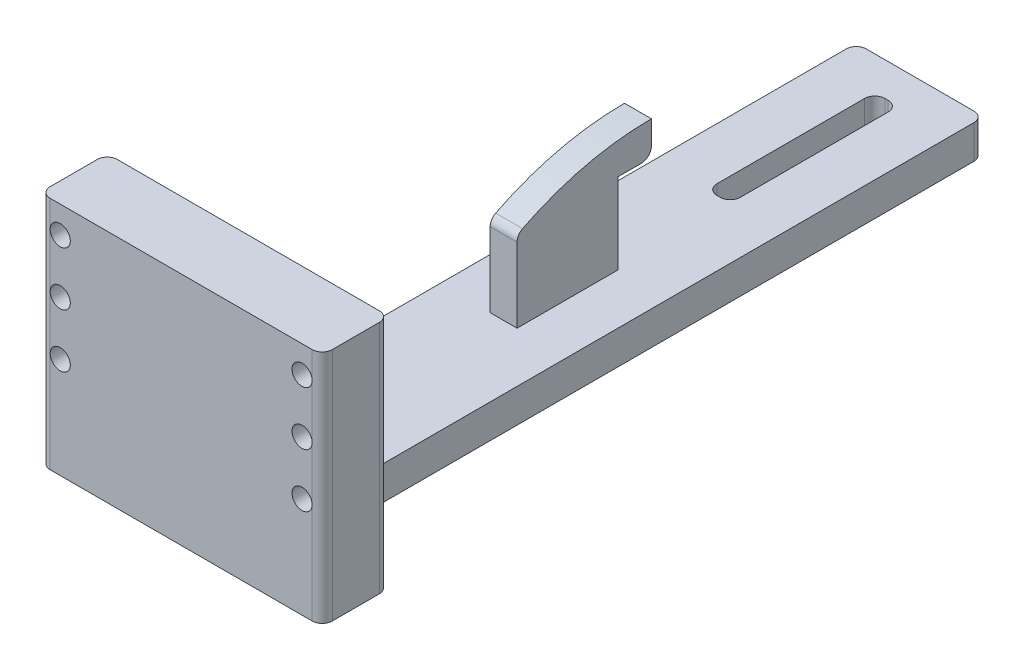
SolidWorks part; units mm, degrees
ref_plane "Front Plane" through (0, 0, 0) normal (0, 0, 1) x (1, 0, 0)
ref_plane "Top Plane" through (0, 0, 0) normal (0, 1, 0) x (1, 0, 0)
ref_plane "Right Plane" through (0, 0, 0) normal (1, 0, 0) x (0, 0, -1)
sketch "Sketch1" plane through (0, 0, 0) normal (0, 1, 0) x (1, 0, 0)
  line L1 (0, 0) -> (-19, 0)
  line L2 (0, 0) -> (0, 110)
  line L3 (0, 110) -> (-19, 110)
  line L4 (-19, 0) -> (-19, 110)
  line L5 (-11.25, 105) -> (-7.75, 105)
  line L6 (-11.25, 105) -> (-11.25, 80)
  line L7 (-11.25, 80) -> (-7.75, 80)
  line L8 (-7.75, 105) -> (-7.75, 80)
  point P9 (-9.5, 105)
  point P10 (-9.5, 110)
  dimension "D1" = 110
  dimension "D2" = 19
  dimension "D3" = 3.5
  dimension "D4" = 5
  dimension "D5" = 25
extrude "Boss-Extrude1" add sketch "Sketch1" along normal blind 5
sketch "Sketch2" plane through (0, 0, 0) normal (1, 0, 0) x (0, 0, -1)
  line L0 (10, 15) -> (10, 35)
  line L2 (0, 5) -> (0, 15)
  line L4 (10, 5) -> (10, 15)
  line L5 (10, 35) -> (0, 35)
  line L6 (0, 35) -> (0, 15)
  line L8 (0, 0) -> (10, 0)
  line L9 (0, 0) -> (0, 5)
  line L11 (10, 0) -> (10, 5)
  line L13 (0, 5) -> (110, 5) construction
  dimension "D1" = 10
  dimension "D2" = 180
  dimension "D3" = 10
  dimension "D4" = 20
  dimension "D5" = 10
extrude "Boss-Extrude2" add sketch "Sketch2" against normal blind 30.5 and the other way blind 11.5
sketch "Sketch3" plane through (0, 0, -10) normal (0, 0, -1) x (-1, 0, 0)
  line L0 (-11.5, 35) -> (30.5, 35) construction
  line L2 (9.5, 35) -> (9.5, 5) construction
  line L3 (19, 5) -> (0, 5) construction
  circle A0 centre (-8.5, 31) radius 1.5
  circle A1 centre (-8.5, 23) radius 1.5
  circle A2 centre (-8.5, 15) radius 1.5
  circle A3 centre (27.5, 15) radius 1.5
  circle A4 centre (27.5, 23) radius 1.5
  circle A5 centre (27.5, 31) radius 1.5
  point P14 (0, 0)
  dimension "D2" = 3
  dimension "D1" = 8
  dimension "D3" = 8
  dimension "D4" = 4
  dimension "D5" = 18
extrude "Cut-Extrude1" cut sketch "Sketch3" against normal blind 10
sketch "Sketch4" plane through (0, 5, 0) normal (0, 1, 0) x (1, 0, 0)
  line L1 (-11.5, 63) -> (-7.5, 63)
  line L2 (-11.5, 63) -> (-11.5, 48)
  line L3 (-11.5, 48) -> (-7.5, 48)
  line L4 (-7.5, 63) -> (-7.5, 48)
  line L5 (0, 110) -> (-19, 110) construction
  line L6 (-19, 10) -> (0, 10) construction
  point P6 (-9.5, 110)
  point P7 (-9.5, 63)
  dimension "D1" = 4
  dimension "D2" = 15
  dimension "D3" = 53
extrude "Boss-Extrude3" add sketch "Sketch4" along normal blind 12
sketch "Sketch5" plane through (-7.5, 0, 0) normal (1, 0, 0) x (0, 0, -1)
  line L0 (63, 17) -> (68, 17)
  line L1 (68, 17) -> (68, 22)
  line L2 (68, 22) -> (78.519, 22) construction
  line L3 (48, 17) -> (63, 17)
  arc A0 (48, 17) -> (68, 22) centre (68, -20.5) cw
  dimension "D1" = 5
  dimension "D2" = 5
extrude "Boss-Extrude4" add sketch "Sketch5" against normal blind 4
fillet "Fillet1" radius 1.5 15 edges at (0, 2.5, -110) (-19, 2.5, -110) (11.5, 17.5, 0) (-30.5, 17.5, 0) (11.5, 17.5, -10) (0, 2.5, -10) (-19, 2.5, -10) (-30.5, 17.5, -10) (-11.25, 2.5, -105) (-7.75, 2.5, -105) (-7.75, 2.5, -80) (-11.25, 2.5, -80) (-9.5, 17, -48) (-9.5, 17, -68) (-9.5, 5, -10)
